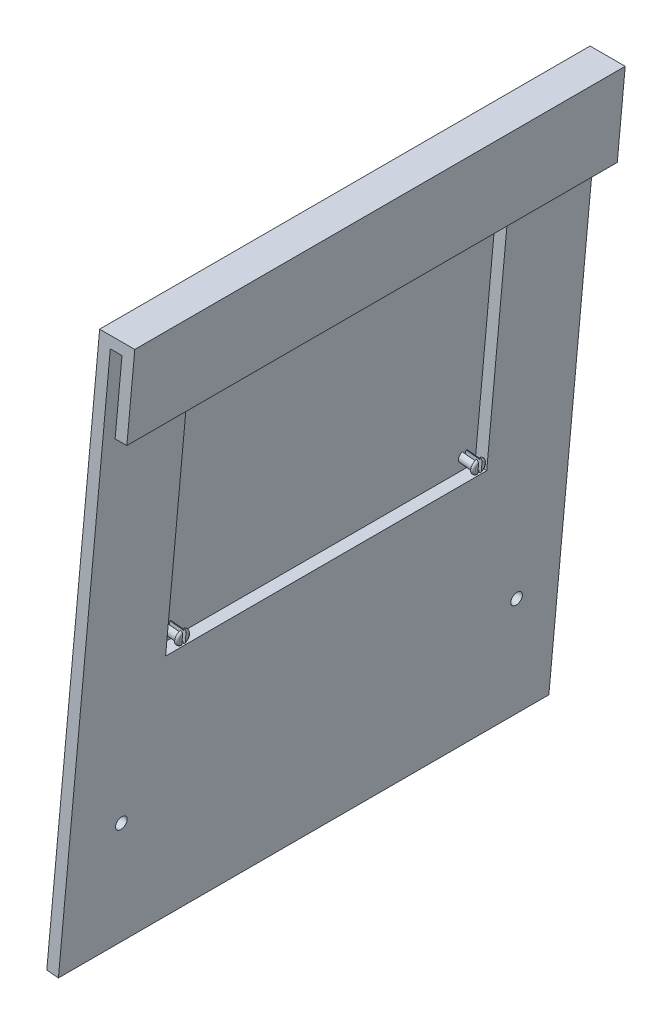
SolidWorks part; units mm, degrees
material "PLA"
ref_plane "Plano frontal" through (0, 0, 0) normal (0, 0, 1) x (1, 0, 0)
ref_plane "Plano superior" through (0, 0, 0) normal (0, 1, 0) x (1, 0, 0)
ref_plane "Plano direito" through (0, 0, 0) normal (1, 0, 0) x (0, 0, -1)
sketch "Esboço1" plane through (0, 0, 0) normal (0, 1, 0) x (1, 0, 0)
  line L0 (0, 225) -> (0, -225)
  line L1 (0, 0) -> (900, 0) construction
  line L2 (900, 247.5) -> (900, -247.5)
  line L3 (0, 225) -> (900, 247.5)
  line L4 (0, -225) -> (900, -247.5)
  dimension "D1" = 900
  dimension "D2" = 450
  dimension "D3" = 495
ref_plane "Plano1" through (0, 550, 0) normal (0, 1, 0) x (1, 0, 0)
sketch "Esboço2" plane through (0, 550, 0) normal (0, 1, 0) x (1, 0, 0)
  line L0 (0, 225) -> (0, -225) construction
  line L1 (0, 0) -> (950, 0) construction
  line L2 (950, 255) -> (950, -255) construction
  line L3 (0, -225) -> (950, -255) construction
  line L4 (0, 225) -> (950, 255) construction
  line L5 (950, -255) -> (950, 255)
  point P3 (0, 0)
  dimension "D1" = 450
  dimension "D2" = 950
  dimension "D3" = 510
sketch "Esboço3" plane through (0, 0, 0) normal (0, 0, 1) x (1, 0, 0)
  line L0 (950, 550) -> (900, 0) construction
  line L1 (0, 550) -> (950, 550) construction
  line L2 (0, 0) -> (900, 0) construction
  line L3 (942.1636, 573.8001) -> (952.1636, 573.8001)
  line L4 (952.1636, 573.8001) -> (946.2826, 509.1081)
  line L5 (946.2826, 509.1081) -> (956.3238, 509.1081)
  line L6 (956.3238, 509.1081) -> (963.114, 583.8001)
  line L7 (963.114, 583.8001) -> (933.0315, 583.8001)
  line L8 (933.0315, 583.8001) -> (887.7636, 85.8535)
  line L9 (887.7636, 85.8535) -> (897.7226, 84.9482)
  line L10 (897.7226, 84.9482) -> (942.1636, 573.8001)
  point P13 (947.1636, 573.8001)
  dimension "D1" = 10
  dimension "D2" = 10
  dimension "D3" = 10
  dimension "D4" = 10
  dimension "D5" = 75
  dimension "D6" = 500
sweep "Varredura2" add profiles "Esboço3" path "Esboço2"
sketch "Esboço4" plane through (872.746, -79.3405, 0) normal (-0.9959, 0.0905, 0) x (0, 0, 1)
  line L0 (0, 665.8753) -> (0, 165.8753) construction
  line L1 (-150, 365.8753) -> (150, 365.8753)
  line L2 (-150, 365.8753) -> (-150, 605.8753)
  line L3 (-150, 605.8753) -> (150, 605.8753)
  line L4 (150, 365.8753) -> (150, 605.8753)
  line L5 (-150, 365.8753) -> (150, 605.8753) construction
  line L6 (-150, 605.8753) -> (150, 365.8753) construction
  line L7 (-255, 665.8753) -> (255, 665.8753) construction
  line L8 (-255, 165.8753) -> (255, 165.8753) construction
  point P0 (0, 485.8753)
  dimension "D1" = 300
  dimension "D2" = 240
  dimension "D3" = 180
sketch "Esboço5" plane through (872.746, -79.3405, 0) normal (-0.9959, 0.0905, 0) x (0, 0, 1)
  line L5 (-150, 605.8753) -> (150, 365.8753) construction
  line L6 (-137.5, 378.8753) -> (137.5, 378.8753)
  line L7 (-137.5, 378.8753) -> (-137.5, 592.8753)
  line L8 (-137.5, 592.8753) -> (137.5, 592.8753)
  line L9 (137.5, 378.8753) -> (137.5, 592.8753)
  line L10 (-137.5, 378.8753) -> (137.5, 592.8753) construction
  line L11 (-137.5, 592.8753) -> (137.5, 378.8753) construction
  point P1 (0, 485.8753)
  point P2 (0, 485.8753)
  dimension "D1" = 275
  dimension "D2" = 214
extrude "Corte-extrusão1" cut sketch "Esboço5" against normal through all and the other way blind 14
extrude "Ressalto-extrusão1" add sketch "Esboço4" along normal blind 15.25
sketch "Esboço6" plane through (872.746, -79.3405, 0) normal (0.9959, -0.0905, 0) x (0, 0, -1)
  line L0 (0, 592.8753) -> (0, 378.8753) construction
  line L1 (137.5, 592.8753) -> (-137.5, 592.8753) construction
  line L2 (-137.5, 378.8753) -> (137.5, 378.8753) construction
  line L3 (137.5, 378.8753) -> (-137.5, 378.8753) construction
  line L4 (-137.5, 378.8753) -> (-137.5, 592.8753) construction
  line L5 (-137.5, 592.8753) -> (137.5, 592.8753) construction
  circle A0 centre (-126.74, 389.5353) radius 4.5
  circle A1 centre (126.74, 389.5353) radius 4.5
  circle A2 centre (-126.74, 581.5253) radius 4.5
  circle A3 centre (126.74, 581.5253) radius 4.5
  dimension "D1" = 9
  dimension "D4" = 10.76
  dimension "D2" = 10.66
  dimension "D3" = 10.76
  dimension "D5" = 11.35
extrude "Ressalto-extrusão2" add sketch "Esboço6" along normal blind 12
sketch "Esboço7" plane through (884.6967, -80.427, 0) normal (0.9959, -0.0905, 0) x (0, 0, -1)
  line L0 (-126.74, 394.0353) -> (-126.74, 385.0353) construction
  circle A0 centre (-126.74, 389.5353) radius 4.5 construction
  circle A1 centre (-126.74, 389.5353) radius 6
  circle A2 centre (126.74, 389.5353) radius 6
  circle A3 centre (126.74, 581.5253) radius 6
  circle A4 centre (-126.74, 581.5253) radius 6
extrude "Ressalto-extrusão3" add sketch "Esboço7" along normal blind 2
fillet "Filete1" radius 2 4 edges at (922.4986, 313.3029, 126.74) (922.4986, 313.3029, -126.74) (939.8805, 504.5044, -126.74) (939.8805, 504.5044, 126.74)
sketch "Esboço8" plane through (886.6885, -80.608, 0) normal (0.9959, -0.0905, 0) x (0, 0, -1)
  line L1 (-128.24, 382.6564) -> (-125.24, 382.6564)
  line L2 (-128.24, 382.6564) -> (-128.24, 396.4141)
  line L3 (-128.24, 396.4141) -> (-125.24, 396.4141)
  line L4 (-125.24, 382.6564) -> (-125.24, 396.4141)
  line L5 (-128.24, 382.6564) -> (-125.24, 396.4141) construction
  line L6 (-128.24, 396.4141) -> (-125.24, 382.6564) construction
  line L7 (125.24, 381.2154) -> (128.24, 381.2154)
  line L8 (125.24, 381.2154) -> (125.24, 397.8551)
  line L9 (125.24, 397.8551) -> (128.24, 397.8551)
  line L10 (128.24, 381.2154) -> (128.24, 397.8551)
  line L11 (125.24, 381.2154) -> (128.24, 397.8551) construction
  line L12 (125.24, 397.8551) -> (128.24, 381.2154) construction
  line L13 (125.24, 573.6401) -> (128.24, 573.6401)
  line L14 (125.24, 573.6401) -> (125.24, 589.4105)
  line L15 (125.24, 589.4105) -> (128.24, 589.4105)
  line L16 (128.24, 573.6401) -> (128.24, 589.4105)
  line L17 (125.24, 573.6401) -> (128.24, 589.4105) construction
  line L18 (125.24, 589.4105) -> (128.24, 573.6401) construction
  line L19 (-128.24, 574.5522) -> (-125.24, 574.5522)
  line L20 (-128.24, 574.5522) -> (-128.24, 588.4984)
  line L21 (-128.24, 588.4984) -> (-125.24, 588.4984)
  line L22 (-125.24, 574.5522) -> (-125.24, 588.4984)
  line L23 (-128.24, 574.5522) -> (-125.24, 588.4984) construction
  line L24 (-128.24, 588.4984) -> (-125.24, 574.5522) construction
  point P0 (-126.74, 389.5353)
  point P6 (126.74, 389.5353)
  point P12 (126.74, 581.5253)
  point P18 (-126.74, 581.5253)
  dimension "D1" = 3
  dimension "D2" = 3
extrude "Corte-extrusão2" cut sketch "Esboço8" against normal up to surface (14 mm away) up to face at (924.9874, 495.315, -126.74)
sketch "Esboço9" plane through (872.746, -79.3405, 0) normal (-0.9959, 0.0905, 0) x (0, 0, 1)
  line L0 (-150, 605.8753) -> (-150, 365.8753) construction
  line L1 (-210, 714.4401) -> (-407.5934, 714.4401)
  line L2 (-210, 714.4401) -> (-210, 135.7738)
  line L3 (-210, 135.7738) -> (-407.5934, 135.7738)
  line L4 (-407.5934, 714.4401) -> (-407.5934, 135.7738)
  line L5 (150, 365.8753) -> (150, 605.8753) construction
  line L6 (210, 714.4401) -> (365.2519, 714.4401)
  line L7 (210, 714.4401) -> (210, 135.7738)
  line L8 (210, 135.7738) -> (365.2519, 135.7738)
  line L9 (365.2519, 714.4401) -> (365.2519, 135.7738)
  dimension "D1" = 60
  dimension "D2" = 60
extrude "Corte-extrusão3" cut sketch "Esboço9" against normal through all both and the other way through all
sketch "Esboço10" plane through (0, 0, 0) normal (0, 0, 1) x (1, 0, 0)
  line L0 (897.7226, 0) -> (952.1636, 573.8001) construction
  line L1 (0, 0) -> (900, 0) construction
sketch "Esboço11" plane through (0, 583.8001, 0) normal (0, 1, 0) x (1, 0, 0)
  line L0 (963.114, 0) -> (0, 0) construction
  line L1 (963.114, 210) -> (963.114, -210) construction
fillet "Filete2" radius 5 4 edges at (916.7351, 404.5393, -150) (905.8708, 285.0322, 0) (927.5994, 524.0465, 0) (916.7351, 404.5393, 150)
sketch "Sketch1" plane through (872.746, -79.3405, 0) normal (-0.9959, 0.0905, 0) x (0, 0, 1)
  circle A0 centre (-175.0637, 629.98) radius 5
extrude "Cut-Extrude1" cut sketch "Sketch1" against normal blind 10
sketch "Sketch2" plane through (872.746, -79.3405, 0) normal (-0.9959, 0.0905, 0) x (0, 0, 1)
  circle A0 centre (174.924, 629.5878) radius 5
extrude "Cut-Extrude2" cut sketch "Sketch2" against normal blind 10
sketch "Sketch3" plane through (872.746, -79.3405, 0) normal (-0.9959, 0.0905, 0) x (0, 0, 1)
  circle A0 centre (164.9113, 263.0028) radius 5
extrude "Cut-Extrude3" cut sketch "Sketch3" against normal blind 10
sketch "Sketch4" plane through (872.746, -79.3405, 0) normal (-0.9959, 0.0905, 0) x (0, 0, 1)
  circle A0 centre (-173.8699, 259.8733) radius 5
extrude "Cut-Extrude4" cut sketch "Sketch4" against normal blind 10
